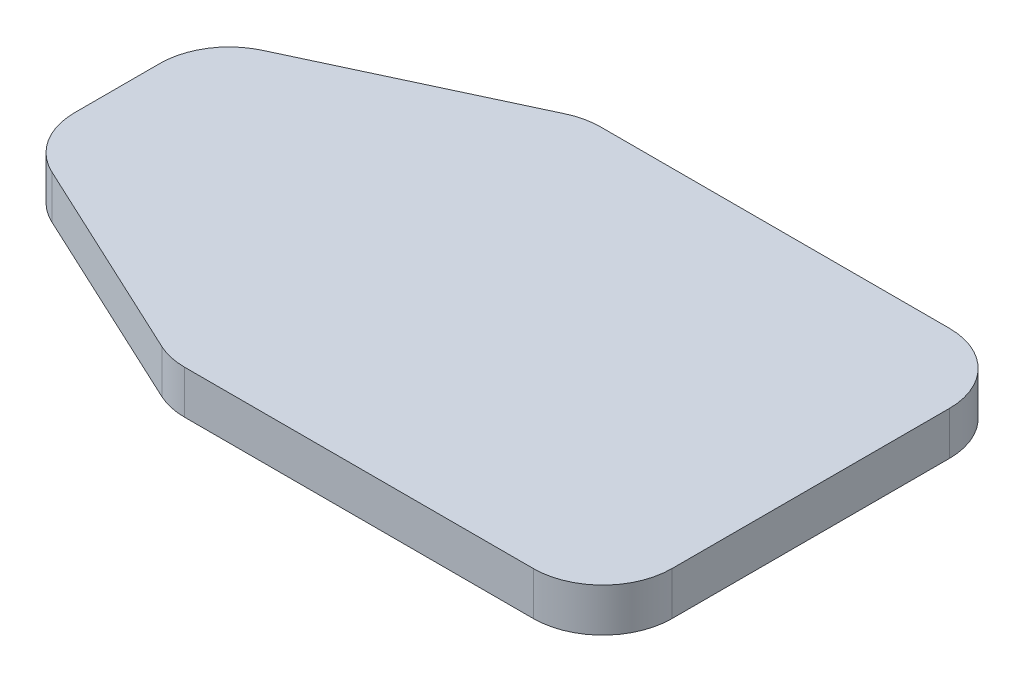
SolidWorks part; units mm, degrees
ref_plane "Front Plane" through (0, 0, 0) normal (0, 0, 1) x (1, 0, 0)
ref_plane "Top Plane" through (0, 0, 0) normal (0, 1, 0) x (1, 0, 0)
ref_plane "Right Plane" through (0, 0, 0) normal (1, 0, 0) x (0, 0, -1)
sketch "Sketch1" plane through (0, 0, 0) normal (0, 1, 0) x (1, 0, 0)
  line L0 (-25.4, 6.35) -> (-6.35, 15.24)
  line L1 (-25.4, 15.24) -> (25.4, 15.24)
  line L2 (-25.4, 15.24) -> (-25.4, -15.24)
  line L3 (-25.4, -15.24) -> (25.4, -15.24)
  line L4 (25.4, 15.24) -> (25.4, -15.24)
  line L5 (-25.4, -6.35) -> (-6.35, -15.24)
  point P4 (0, 15.24)
  point P5 (-25.4, 0)
  point P11 (0, 0)
  dimension "D1" = 30.48
  dimension "D2" = 50.8
  dimension "D3" = 19.05
  dimension "D4" = 8.89
extrude "Boss-Extrude1" add sketch "Sketch1" along normal blind 3.175 contours L2 L5 L3 L4 L1 L0 region at (2.3395, 0, 0)
fillet "Fillet2" radius 5.08 6 edges at (25.4, 1.5875, 15.24) (25.4, 1.5875, -15.24) (-6.35, 1.5875, -15.24) (-25.4, 1.5875, -6.35) (-25.4, 1.5875, 6.35) (-6.35, 1.5875, 15.24)
